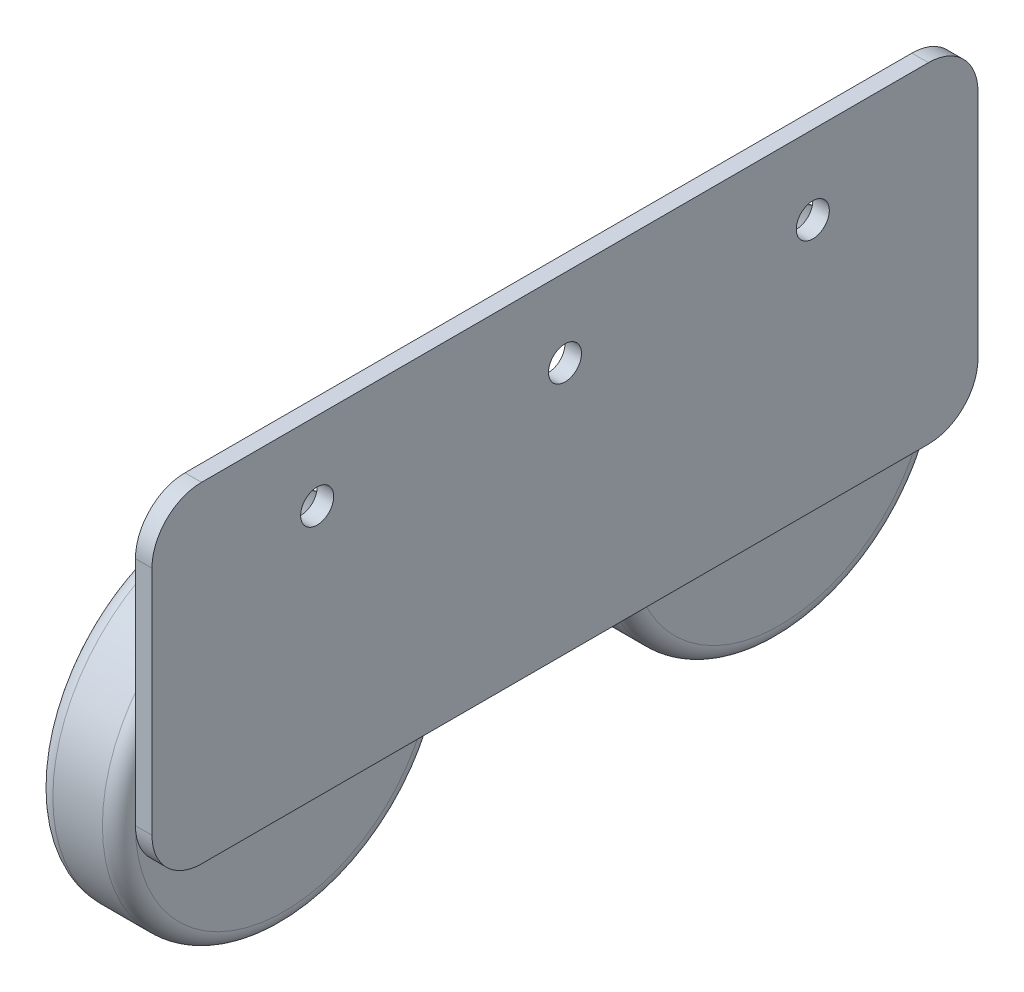
SolidWorks part; units mm, degrees
ref_plane "Front Plane" through (0, 0, 0) normal (0, 0, 1) x (1, 0, 0)
ref_plane "Top Plane" through (0, 0, 0) normal (0, 1, 0) x (1, 0, 0)
ref_plane "Right Plane" through (0, 0, 0) normal (1, 0, 0) x (0, 0, -1)
sketch "Sketch1" plane through (0, 0, 0) normal (0, 0, 1) x (1, 0, 0)
  line L0 (0, 15.425) -> (0, -15.425) construction
  line L1 (-29.3, 0) -> (29.3, 0) construction
  line L3 (0, 10) -> (-1, 10)
  line L4 (0, 10) -> (0, -10)
  line L5 (0, -10) -> (-1, -10)
  line L6 (-1, 10) -> (-1, -10)
  dimension "D1" = 1
  dimension "D2" = 20
extrude "Boss-Extrude1" add sketch "Sketch1" along normal blind 50
sketch "Sketch3" plane through (-1, 0, 0) normal (-1, 0, 0) x (0, 0, 1)
  line L0 (10, 14.6885) -> (10, -17.5617) construction
  line L1 (40, 14.6885) -> (40, -17.5694) construction
  line L2 (50, 10) -> (50, -10) construction
  line L3 (0, 10) -> (0, -10) construction
  line L4 (-5.139, -8) -> (55.352, -8) construction
  line L5 (50, -10) -> (0, -10) construction
  dimension "D1" = 10
  dimension "D2" = 10
  dimension "D3" = 2
ref_plane "Mid Plane" through (0, 0, 25) normal (0, 0, 1) x (1, 0, 0)
sketch "Sketch6" plane through (-1, 0, 0) normal (-1, 0, 0) x (0, 0, 1)
  line L0 (10, 14.6885) -> (10, -17.5617) construction
  line L1 (-5.139, -8) -> (55.352, -8) construction
  circle A0 centre (10, -8) radius 1
  dimension "D1" = 2
extrude "Boss-Extrude2" add sketch "Sketch6" along normal blind 1
sketch "Sketch7" plane through (-2, 0, 0) normal (-1, 0, 0) x (0, 0, 1)
  circle A0 centre (10, -8) radius 10
  dimension "D1" = 20
extrude "Boss-Extrude3" add sketch "Sketch7" along normal blind 5
sketch "Sketch9" plane through (-7, 0, 0) normal (-1, 0, 0) x (0, 0, 1)
  line L0 (10, 14.6885) -> (10, -17.5617) construction
  line L1 (-5.139, -8) -> (55.352, -8) construction
  circle A0 centre (10, -8) radius 8
  circle A1 centre (10, -8) radius 10 construction
  circle A2 centre (10, -8) radius 1.5
  dimension "D1" = 2
  dimension "D2" = 3
extrude "Cut-Extrude1" cut sketch "Sketch9" against normal offset from surface (2 mm away) 3 up to face at (-2, -8, 20)
fillet "Fillet3" radius 1 1 edges at (-7, -8, 11.5)
fillet "Fillet4" radius 1 2 edges at (-2, -8, 20) (-7, -8, 20)
fillet "Fillet6" radius 1 1 edges at (-7, -8, 18)
fillet "Fillet7" radius 1 1 edges at (-5, -8, 18)
mirror "Mirror2" about plane through (0, 0, 25) normal (0, 0, 1) of "Fillet6", "Fillet4", "Fillet3", "Cut-Extrude1", "Boss-Extrude3", "Boss-Extrude2", "Fillet7"
fillet "Fillet8" radius 3 4 edges at (-0.5, -10, 0) (-0.5, 10, 0) (-0.5, -10, 50) (-0.5, 10, 50)
sketch "Sketch10" plane through (-1, 0, 0) normal (-1, 0, 0) x (0, 0, 1)
  line L0 (25, 19.5908) -> (25, -19.9228) construction
  line L1 (25, -0.55) -> (25, 0.55) construction
  line L2 (-4.1917, 5.2609) -> (60.6475, 5.2609) construction
  line L3 (10, 14.6885) -> (10, -17.5617) construction
  line L4 (10, 16.4694) -> (10, 2.0686) construction
  line L5 (40, 16.4694) -> (40, 2.9199) construction
  line L6 (40, 14.6885) -> (40, -17.5694) construction
  circle A0 centre (10, 5.2609) radius 1
  circle A1 centre (25, 5.2609) radius 1
  circle A2 centre (40, 5.2609) radius 1
  dimension "D1" = 2
  dimension "D2" = 2
extrude "Cut-Extrude2" cut sketch "Sketch10" against normal through all both and the other way through all
